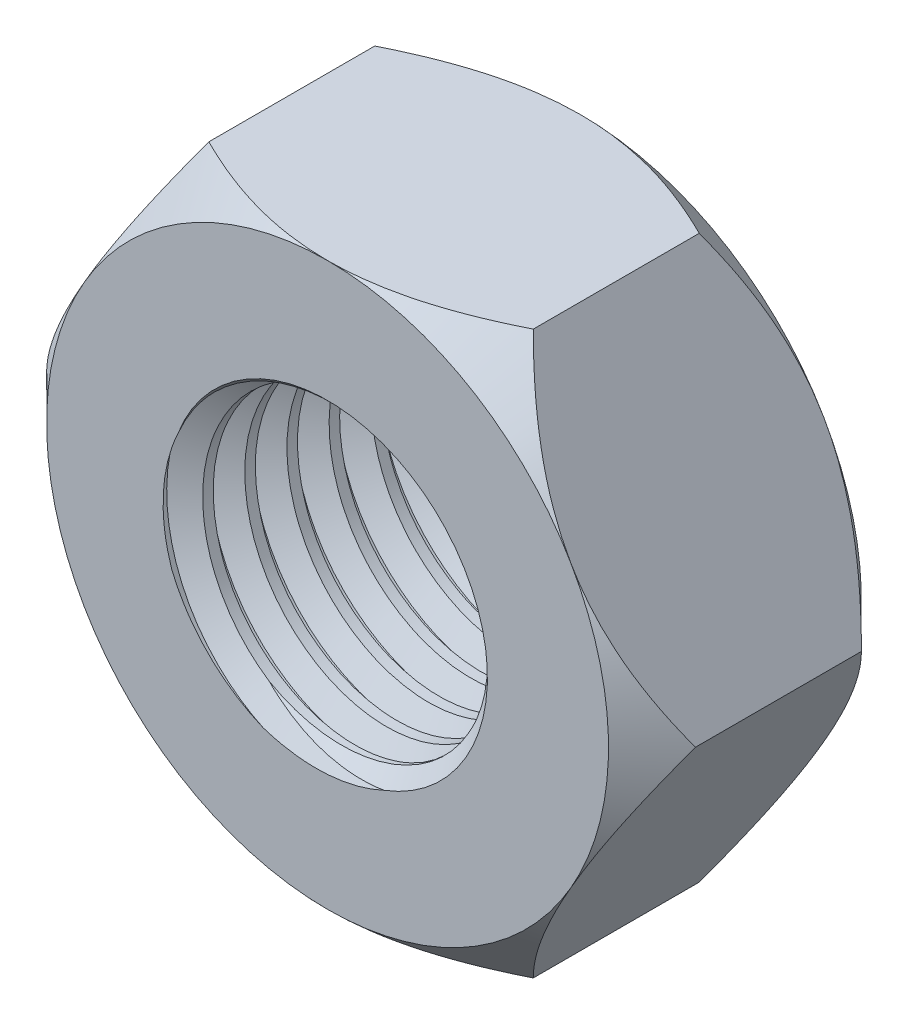
SolidWorks part; units mm, degrees
ref_plane "Front Plane" through (0, 0, 0) normal (0, 0, 1) x (1, 0, 0)
ref_plane "Top Plane" through (0, 0, 0) normal (0, 1, 0) x (1, 0, 0)
ref_plane "Right Plane" through (0, 0, 0) normal (1, 0, 0) x (0, 0, -1)
sketch "Sketch2" plane through (0, 0, 0) normal (0, 0, 1) x (1, 0, 0)
  line L1 (-11.547, 0) -> (-5.7735, -10)
  line L2 (-5.7735, -10) -> (5.7735, -10)
  line L3 (5.7735, -10) -> (11.547, 0)
  line L4 (11.547, 0) -> (5.7735, 10)
  line L5 (5.7735, 10) -> (-5.7735, 10)
  line L6 (-5.7735, 10) -> (-11.547, 0)
  circle A0 centre (0, 0) radius 10 construction
  dimension "D1" = 20
extrude "Boss-Extrude1" add sketch "Sketch2" along normal mid plane 9
sketch "Sketch3" plane through (0, 0, 4.5) normal (0, 0, 1) x (1, 0, 0)
  line L0 (-5.7735, 10) -> (-11.547, 0) construction
  circle A0 centre (0, 0) radius 10
extrude "Cut-Extrude1" cut sketch "Sketch3" against normal through all draft 45 flip side to cut
mirror "Mirror1" about plane through (0, 0, 0) normal (0, 0, 1) of "Cut-Extrude1"
sketch "Sketch4" plane through (0, 0, 4.5) normal (0, 0, 1) x (1, 0, 0)
  circle A0 centre (0, 0) radius 5.19
  dimension "D1" = 10.38
extrude "Cut-Extrude2" cut sketch "Sketch4" against normal through all
chamfer "Chamfer1" distance 0.5 angle 45 1 edges at (5.19, 0, 4.5)
chamfer "Chamfer2" distance 0.5 angle 45 1 edges at (5.19, 0, -4.5)
thread "Thread1" pitch 1.5 method cut profile "Thread Profile1" start angle 0, offset 2, length 0, pitch 1.5, diameter 10.38
ref_plane "Plane1" through (5.19, 0, -6) normal (0, -1, 0) x (1, 0, 0)
sketch "Thread Profile1" plane through (5.19, 0, -6) normal (0, -1, 0) x (1, 0, 0)
  line L0 (0, 0) -> (0, 1.5) construction
  line L1 (0, 0) -> (0.8119, 0.4687)
  line L2 (0.8119, 0.4687) -> (0.8119, 0.6562)
  line L3 (0.8119, 0.6562) -> (0, 1.125)
  line L4 (0.8119, 0.5625) -> (0, 0.5625) construction
  line L11 (0, 0) -> (0, 1.125)
  point P2 (0, 0)
  dimension "Pitch" = 1.5
  dimension "Profile_Angle" = 60
  dimension "Profile_Land" = 0.1875
  dimension "Profile_Height" = 0.8119
